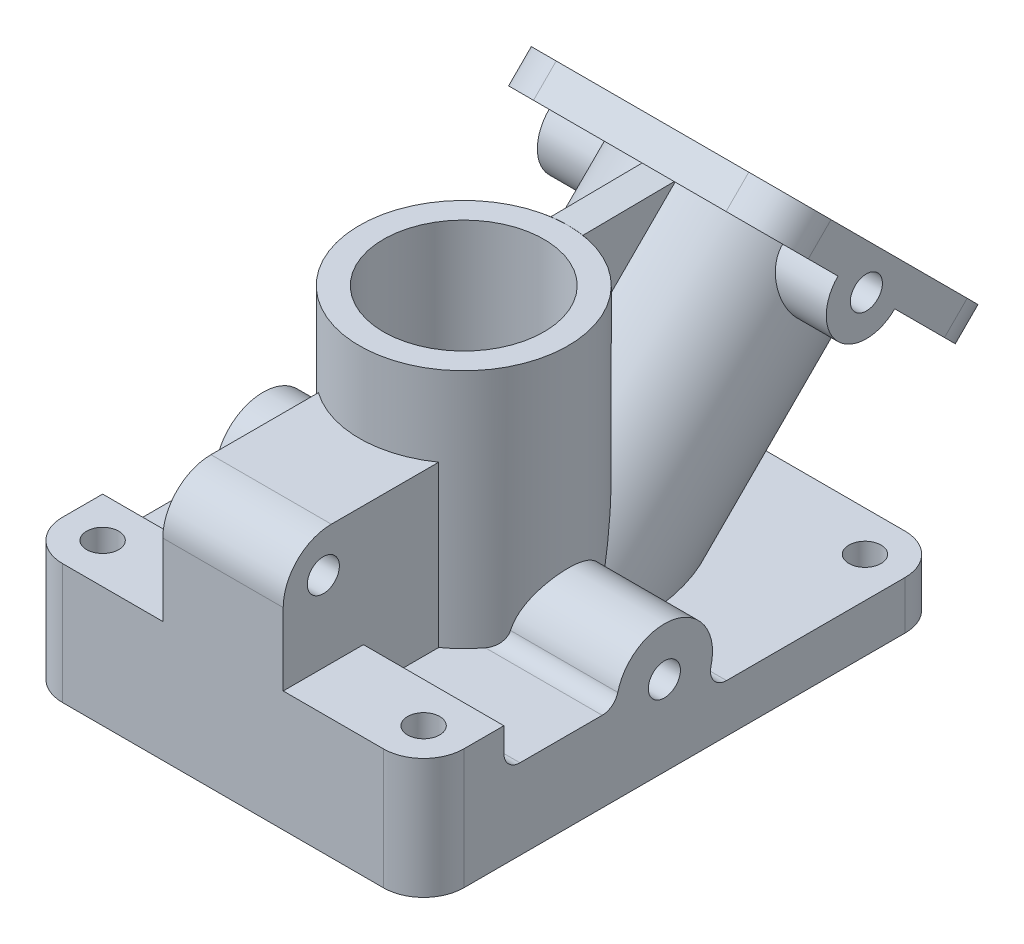
SolidWorks part; units mm, degrees
material "PET"
ref_plane "Alzado" through (0, 0, 0) normal (0, 0, 1) x (1, 0, 0)
ref_plane "Planta" through (0, 0, 0) normal (0, 1, 0) x (1, 0, 0)
ref_plane "Vista lateral" through (0, 0, 0) normal (1, 0, 0) x (0, 0, -1)
other "plastico pet"
sketch "Croquis1" plane through (0, 0, 0) normal (0, 1, 0) x (1, 0, 0)
  line L1 (-25, 32.5) -> (25, 32.5)
  line L2 (-25, 32.5) -> (-25, -32.5)
  line L3 (-25, -32.5) -> (25, -32.5)
  line L4 (25, 32.5) -> (25, -32.5)
  line L5 (-25, 32.5) -> (25, -32.5) construction
  line L6 (-25, -32.5) -> (25, 32.5) construction
  point P0 (0, 0)
  dimension "D1" = 65
  dimension "D2" = 50
extrude "Saliente-Extruir1" add sketch "Croquis1" along normal blind 6
sketch "Croquis2" plane through (0, 0, 0) normal (1, 0, 0) x (0, 0, -1)
  line L0 (-2.5, 0) -> (-2.5, 40) construction
  line L1 (-32.5, 0) -> (32.5, 0) construction
  dimension "D1" = 30
  dimension "D2" = 40
ref_plane "Plano1" through (0, 40, 0) normal (0, 1, 0) x (1, 0, 0)
sketch "Croquis3" plane through (0, 40, 0) normal (0, 1, 0) x (1, 0, 0)
  circle A0 centre (0, -2.5) radius 13
  circle A1 centre (0, -2.5) radius 10
  dimension "D1" = 20
  dimension "D2" = 26
extrude "Saliente-Extruir2" add sketch "Croquis3" against normal up to surface (34 mm away) up to face at (0, 6, 0)
sketch "Croquis8" plane through (0, 0, 0) normal (1, 0, 0) x (0, 0, -1)
  line L0 (-2.5, 0) -> (32.5, 35)
  line L1 (-2.5, 0) -> (-2.5, 40) construction
  line L2 (-32.5, 0) -> (32.5, 0) construction
  dimension "D1" = 45
  dimension "D2" = 35
ref_plane "Plano3" through (0, 35, -32.5) normal (0, 0.7071, -0.7071) x (-1, 0, 0)
sketch "Croquis9" plane through (0, 35, -32.5) normal (0, 0.7071, -0.7071) x (-1, 0, 0)
  circle A0 centre (0, -1.7678) radius 13
  circle A1 centre (0, -1.7678) radius 10
  dimension "D1" = 20
  dimension "D2" = 26
extrude "Saliente-Extruir3" add sketch "Croquis9" against normal up to surface (52.2444 mm away) up to face at (0, 6, 15.5)
extrude "Cortar-Extruir1" cut sketch "Croquis3<3>" against normal up to surface (34 mm away) contours A1 region at (0, 40, 2.5) up to face at (0, 6, -4.4424)
sketch "Croquis3<3>" plane through (0, 40, 0) normal (0, 1, 0) x (1, 0, 0) same geometry as "Croquis3"
sketch "Croquis10" plane through (0, 35, -32.5) normal (0, 0.7071, -0.7071) x (-1, 0, 0)
  line L5 (-18, 16.2322) -> (18, 16.2322)
  line L10 (-18, 16.2322) -> (-18, -19.7678)
  line L11 (-18, -19.7678) -> (18, -19.7678)
  line L12 (18, 16.2322) -> (18, -19.7678)
  line L13 (-18, 16.2322) -> (18, -19.7678) construction
  line L14 (-18, -19.7678) -> (18, 16.2322) construction
  circle A0 centre (0, -1.7678) radius 10 construction
  circle A1 centre (0, -1.7678) radius 10
  point P0 (0, 0)
  point P1 (0, 0)
  dimension "D1" = 36
  dimension "D2" = 36
extrude "Saliente-Extruir4" add sketch "Croquis10" against normal blind 4
sketch "Croquis12" plane through (0, 35, -32.5) normal (0, 0.7071, -0.7071) x (-1, 0, 0)
  line L1 (-18, -19.7678) -> (18, -19.7678) construction
  line L2 (18, -19.7678) -> (18, 16.2322) construction
  circle A1 centre (13, -14.7678) radius 2
  dimension "D1" = 4
  dimension "D2" = 5
  dimension "D3" = 5
extrude "Cortar-Extruir7" cut sketch "Croquis12" along normal up to surface (-4 mm away) contours A1 up to face at (0, 40.114, -21.7292)
pattern_linear "MatrizL1" count 2 spacing 26 along (0, 0.7071, 0.7071) count 2 spacing 26 along (1, 0, 0) of "Cortar-Extruir7"
sketch "Croquis13" plane through (18, 0, 0) normal (1, 0, 0) x (0, 0, -1)
  line L0 (18.1937, 43.6495) -> (43.6495, 18.1937) construction
  line L1 (18.1937, 43.6495) -> (43.6495, 18.1937)
  line L2 (21.7292, 40.114) -> (40.114, 21.7292) construction
  line L3 (-2.5, 0) -> (32.5, 35) construction
  arc A0 (26.136, 35.7071) -> (33.2071, 28.636) centre (29.6716, 32.1716) ccw
  circle A1 centre (29.6716, 32.1716) radius 2
  circle A2 centre (29.6716, 32.1716) radius 2
  line M5 (18.1937, 43.6495) -> (43.6495, 18.1937)
  dimension "D1" = 10
  dimension "D2" = 4
extrude "Saliente-Extruir6" add sketch "Croquis13" against normal up to surface (5.0021 mm away) contours A1 L1 A0 region at (18, 30.4996, -27.9996) up to face at (0, 17.4424, -17.4424)
extrude "Cortar-Extruir8" cut sketch "Croquis13<3>" against normal up to surface (8.5198 mm away) contours A1 M5 | A1 M5 region at (18, 32.7718, -30.2718) region at (18, 31.5714, -29.0714) up to face at (0, 40.8211, -26.6789)
sketch "Croquis13<3>" plane through (18, 0, 0) normal (1, 0, 0) x (0, 0, -1) same geometry as "Croquis13"
sketch "Croquis14" plane through (-18, 0, 0) normal (-1, 0, 0) x (0, 0, 1)
  line L0 (-43.6495, 18.1937) -> (-18.1937, 43.6495) construction
  line L1 (-43.6495, 18.1937) -> (-18.1937, 43.6495)
  line L2 (2.5, 0) -> (-32.5, 35) construction
  arc A1 (-33.2071, 28.636) -> (-26.136, 35.7071) centre (-29.6716, 32.1716) ccw
  circle A2 centre (-29.6716, 32.1716) radius 2
  line M6 (-43.6495, 18.1937) -> (-18.1937, 43.6495)
  dimension "D1" = 4
  dimension "D2" = 10
extrude "Saliente-Extruir7" add sketch "Croquis14" against normal up to surface (5.558 mm away) contours A2 L1 A1 region at (-18, 30.4996, -27.9996) up to face at (-0.0228, 29.2608, -29.0602)
extrude "Cortar-Extruir9" cut sketch "Croquis14<3>" against normal up to surface (8.0063 mm away) contours A2 M6 | A2 M6 region at (-18, 32.7718, -30.2718) region at (-18, 31.5714, -29.0714) up to face at (9.9715, 30.2356, -29.1696)
sketch "Croquis14<3>" plane through (-18, 0, 0) normal (-1, 0, 0) x (0, 0, 1) same geometry as "Croquis14"
ref_plane "Plano4" through (25, 0, 0) normal (1, 0, 0) x (0, 0, -1)
sketch "Croquis16" plane through (25, 0, 0) normal (1, 0, 0) x (0, 0, -1)
  line L0 (-22.5, 12) -> (-22.5, 6)
  line L1 (-32.5, 0) -> (32.5, 0) construction
  line L3 (-2.5, 0) -> (-2.5, 40) construction
  line L4 (-32.5, 6) -> (32.5, 6) construction
  line L5 (5.246, 6) -> (32.5, 6)
  line L6 (-10.246, 10) -> (-20.5, 10)
  line L7 (-22.5, 12) -> (-22.5, 15)
  line L8 (-22.5, 15) -> (-32.5, 15)
  line L9 (-32.5, 15) -> (-32.5, 6)
  line L10 (-15.5, 40) -> (-15.5, 6) construction
  line L11 (-15.5, 10) -> (-15.5, 6)
  line L12 (-32.5, 6) -> (32.5, 6)
  arc A2 (3.3095, 8.5) -> (-8.3095, 11.5) centre (-2.5, 10) ccw
  circle A3 centre (-2.5, 10) radius 2
  arc A4 (-20.5, 10) -> (-22.5, 12) centre (-20.5, 12) cw
  arc A5 (-10.246, 10) -> (-8.3095, 11.5) centre (-10.246, 12) ccw
  arc A6 (5.246, 6) -> (3.3095, 8.5) centre (5.246, 8) cw
  point P19 (-22.5, 10)
  point P22 (-8.5, 10)
  dimension "D2" = 12
  dimension "D3" = 4
  dimension "D8" = 2
  dimension "D1" = 10
  dimension "D4" = 10
  dimension "D5" = 5
  dimension "D6" = 9
  dimension "D7" = 14
extrude "Saliente-Extruir8" add sketch "Croquis16" against normal up to surface (25 mm away) contours L12 A6 A2 A5 L6 L11 A3 region at (25, 9.9252, 4.7248) up to face at (0, 17.4424, 2.5)
sketch "Croquis17" plane through (0, 6, 0) normal (0, 1, 0) x (1, 0, 0)
  line L0 (-7.5, -32.5) -> (7.5, -32.5)
  line L1 (-25, -32.5) -> (25, -32.5) construction
  line L2 (-7.5, -32.5) -> (-7.5, -13.1184)
  line L3 (7.5, -32.5) -> (7.5, -13.1184)
  line L4 (0, -32.5) -> (0, -2.5) construction
  line L5 (0, -15.5) -> (25, -15.5) construction
  line L6 (0, -15.5) -> (7.5, -15.5)
  circle A0 centre (0, -2.5) radius 13 construction
  arc A1 (0, -15.5) -> (10.4403, -10.246) centre (0, -2.5) ccw construction
  arc A2 (-12.5141, 1.0208) -> (0, -15.5) centre (0, -2.5) ccw construction
  arc A3 (-7.5, -13.1184) -> (7.5, -13.1184) centre (0, -2.5) ccw
  arc A4 (0, -15.5) -> (7.5, -13.1184) centre (0, -2.5) ccw
  arc A5 (-7.5, -13.1184) -> (0, -15.5) centre (0, -2.5) ccw
  point P5 (0, -32.5)
  line M10 (-25, -32.5) -> (25, -32.5)
  line M12 (25, -15.5) -> (0, -15.5)
  arc M13 (0, -15.5) -> (-12.5141, 1.0208) centre (0, -2.5) cw
  dimension "D1" = 15
  dimension "D2" = 19.3816
extrude "Saliente-Extruir9" add sketch "Croquis17" along normal blind 24 contours L4 L0 L3 M12 | L4 L2 M10 M13 | A3 L3 M12 region at (-3.832, 6, 23.6051) region at (3.75, 6, 24) region at (5.6611, 6, 14.7983)
sketch "Croquis18" plane through (7.5, 0, 0) normal (1, 0, 0) x (0, 0, -1)
  line L0 (-32.5, 30) -> (-32.5, 6) construction
  line L1 (-32.5, 30) -> (-13.1184, 30) construction
  line L2 (-32.5, 24) -> (-32.5, 6)
  line L3 (-26.5, 30) -> (-13.1184, 30)
  line L4 (-32.5, 30) -> (-32.5, 6)
  line L5 (-32.5, 30) -> (-13.1184, 30)
  circle A0 centre (-27.5, 25) radius 2
  arc A1 (-26.5, 30) -> (-32.5, 24) centre (-26.5, 24) ccw
  line M7 (-13.1184, 30) -> (-32.5, 30)
  line M8 (-32.5, 30) -> (-32.5, 6)
  dimension "D1" = 6
  dimension "D2" = 4
  dimension "D3" = 5
  dimension "D4" = 5
extrude "Cortar-Extruir10" cut sketch "Croquis18" against normal up to surface (15 mm away) contours A0 | A1 M7 M8 region at (7.5, 28.6598, 31.1598) region at (7.5, 25, 27.5) up to face at (-7.5, 18, 22.8092)
extrude "Saliente-Extruir10" add sketch "Croquis16<5>" against normal up to surface (17.5 mm away) contours L9 L12 L0 L7 L8 | L6 A4 L0 L12 L11 region at (25, 8.0728, 19.0908) region at (25, 10.5, 27.5) up to face at (7.5, 25, 25.5)
sketch "Croquis16<5>" plane through (25, 0, 0) normal (1, 0, 0) x (0, 0, -1) same geometry as "Croquis16"
ref_plane "Plano5" through (-25, 0, 0) normal (1, 0, 0) x (0, 0, -1)
sketch "Croquis19" plane through (-25, 0, 0) normal (1, 0, 0) x (0, 0, -1)
  line L8 (-32.5, 15) -> (-32.5, 0) construction
  line L9 (-22.5, 15) -> (-32.5, 15) construction
  line L10 (-22.5, 15) -> (-22.5, 12) construction
  line L11 (-10.246, 10) -> (-20.5, 10) construction
  line L13 (-15.373, 10) -> (-15.373, 6)
  line L14 (-32.5, 15) -> (-32.5, 6)
  line L15 (-22.5, 15) -> (-32.5, 15)
  line L16 (-22.5, 15) -> (-22.5, 12)
  line L17 (-10.246, 10) -> (-20.5, 10)
  line L18 (5.246, 6) -> (-32.5, 6)
  circle A1 centre (-2.5, 10) radius 2
  circle A2 centre (-2.5, 10) radius 2
  arc A6 (3.3095, 8.5) -> (5.246, 6) centre (5.246, 8) ccw construction
  arc A7 (-22.5, 12) -> (-20.5, 10) centre (-20.5, 12) ccw construction
  arc A8 (-10.246, 10) -> (-8.3095, 11.5) centre (-10.246, 12) ccw construction
  arc A9 (3.3095, 8.5) -> (-8.3095, 11.5) centre (-2.5, 10) ccw construction
  arc A10 (3.3095, 8.5) -> (5.246, 6) centre (5.246, 8) ccw
  arc A11 (-22.5, 12) -> (-20.5, 10) centre (-20.5, 12) ccw
  arc A12 (-10.246, 10) -> (-8.3095, 11.5) centre (-10.246, 12) ccw
  arc A13 (3.3095, 8.5) -> (-8.3095, 11.5) centre (-2.5, 10) ccw
  dimension "D1" = 0
extrude "Saliente-Extruir11" add sketch "Croquis19" along normal up to surface (14.5597 mm away) contours A10 A13 A12 L17 L13 L18 A2 region at (-25, 9.9333, 4.6795) up to face at (2.4858, 17.4011, 7.6488)
extrude "Saliente-Extruir12" add sketch "Croquis19<3>" along normal up to surface (17.5 mm away) contours A11 L16 L15 L14 L18 L13 L17 region at (-25, 9.9025, 25.4156) up to face at (-7.5, 25, 29.5)
sketch "Croquis19<3>" plane through (-25, 0, 0) normal (1, 0, 0) x (0, 0, -1) same geometry as "Croquis19"
fillet "Redondeo1" radius 5 4 edges at (25, 7.5, 32.5) (25, 3, -32.5) (-25, 3, -32.5) (-25, 7.5, 32.5)
fillet "Redondeo2" radius 6 4 edges at (18, 45.0637, -19.6079) (-18, 45.0637, -19.6079) (-18, 19.6079, -45.0637) (18, 19.6079, -45.0637)
ref_plane "Plano6" through (0, 15, 0) normal (0, 1, 0) x (1, 0, 0)
sketch "Croquis21" plane through (0, 15, 0) normal (0, 1, 0) x (1, 0, 0)
  line L0 (-7.5, -32.5) -> (-20, -32.5) construction
  line L1 (-25, -25.5629) -> (-25, 25.5629) construction
  circle A0 centre (-20, -27.5) radius 2
  dimension "D1" = 4
  dimension "D2" = 5
  dimension "D3" = 5
extrude "Cortar-Extruir11" cut sketch "Croquis21" against normal up to surface (15 mm away) up to face at (0, 0, 0)
pattern_linear "MatrizL2" count 2 spacing 40 along (1, 0, 0) count 2 spacing 55 along (0, 0, -1) of "Cortar-Extruir11"
sketch "Croquis22" plane through (0, 0, 0) normal (1, 0, 0) x (0, 0, -1)
  line L0 (10.5, 40) -> (21.7292, 40.114)
  line L1 (21.7292, 40.114) -> (10.5, 28.8848) construction
  line L2 (18.1937, 43.6495) -> (22.4363, 39.4069) construction
rib "Nervio2" sketch "Croquis22" sketch "Croquis22" thickness 4 extrusion direction parallel to sketch draft on no parameters "D1"=4
sketch "Croquis23" plane through (0, 0, 0) normal (1, 0, 0) x (0, 0, -1)
  line L0 (32.5, 6) -> (32.5572, 14.1725)
  line L4 (24.3848, 6) -> (40.114, 21.7292) construction
  point P5 (0, 0)
  point P6 (0, 0)
  point P7 (0, 0)
  point P10 (0, 0)
rib "Nervio13" sketch "Croquis23" sketch "Croquis23" thickness 4 extrusion direction parallel to sketch draft on no parameters "D1"=4
